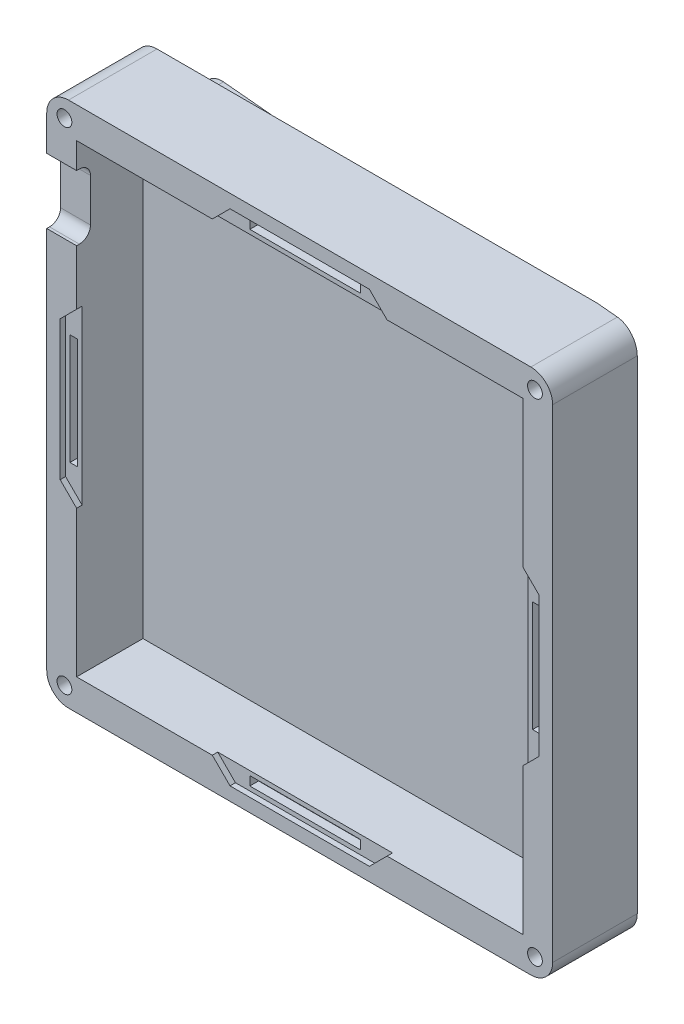
SolidWorks part; units mm, degrees
ref_plane "Front Plane" through (0, 0, 0) normal (1, 0, 0) x (0, 1, 0)
ref_plane "Top Plane" through (0, 0, 0) normal (0, 0, 1) x (0, 1, 0)
ref_plane "Right Plane" through (0, 0, 0) normal (0, 1, 0) x (-1, 0, 0)
sketch "Sketch1" plane through (0, 0, 0) normal (0, 0, 1) x (0, 1, 0)
  line L1 (-55.3847, -53.0098) -> (55.3847, -53.0098) construction
  line L2 (-55.3847, -53.0098) -> (-55.3847, 53.0098) construction
  line L3 (-55.3847, 53.0098) -> (55.3847, 53.0098) construction
  line L4 (55.3847, -53.0098) -> (55.3847, 53.0098) construction
  line L5 (-55.3847, -53.0098) -> (55.3847, 53.0098) construction
  line L6 (-55.3847, 53.0098) -> (55.3847, -53.0098) construction
  line L7 (-60.4647, -58.0898) -> (60.4647, -58.0898)
  line L8 (-60.4647, -58.0898) -> (-60.4647, 58.0898)
  line L9 (-60.4647, 58.0898) -> (60.4647, 58.0898)
  line L10 (60.4647, -58.0898) -> (60.4647, 58.0898)
  line L11 (-60.4647, -58.0898) -> (60.4647, 58.0898) construction
  line L12 (-60.4647, 58.0898) -> (60.4647, -58.0898) construction
  line L13 (-52.3875, -50.0126) -> (52.3875, -50.0126) construction
  line L14 (-52.3875, -50.0126) -> (-52.3875, 50.0126) construction
  line L15 (-52.3875, 50.0126) -> (52.3875, 50.0126) construction
  line L16 (52.3875, -50.0126) -> (52.3875, 50.0126) construction
  line L17 (-52.3875, -50.0126) -> (52.3875, 50.0126) construction
  line L18 (-52.3875, 50.0126) -> (52.3875, -50.0126) construction
  point P0 (0, 0)
  point P6 (0, 0)
  point P11 (0, 0)
  dimension "D1" = 106.0196
  dimension "D2" = 110.7694
  dimension "D3" = 5.08
  dimension "D4" = 5.08
  dimension "D5" = 104.775
  dimension "D6" = 100.0252
extrude "Boss-Extrude1" add sketch "Sketch1" along normal blind 5.08
sketch "Sketch2" plane through (0, 0, 5.08) normal (0, 0, 1) x (1, 0, 0)
  line L1 (58.0898, -60.4647) -> (-58.0898, -60.4647)
  line L2 (58.0898, -60.4647) -> (58.0898, 60.4647)
  line L3 (58.0898, 60.4647) -> (-58.0898, 60.4647)
  line L4 (-58.0898, -60.4647) -> (-58.0898, 60.4647)
  line L5 (58.0898, -60.4647) -> (-58.0898, 60.4647) construction
  line L6 (58.0898, 60.4647) -> (-58.0898, -60.4647) construction
  line L7 (50.2688, -52.324) -> (-50.2688, -52.324) construction
  line L8 (50.2688, -52.324) -> (50.2688, 52.324) construction
  line L9 (50.2688, 52.324) -> (-50.2688, 52.324) construction
  line L10 (-50.2688, -52.324) -> (-50.2688, 52.324) construction
  line L11 (50.2688, -52.324) -> (-50.2688, 52.324) construction
  line L12 (50.2688, 52.324) -> (-50.2688, -52.324) construction
  line L13 (-51.2296, -53.324) -> (51.2296, -53.324)
  line L14 (-51.2296, -53.324) -> (-51.2296, 53.324)
  line L15 (-51.2296, 53.324) -> (51.2296, 53.324)
  line L16 (51.2296, -53.324) -> (51.2296, 53.324)
  line L17 (-51.2296, -53.324) -> (51.2296, 53.324) construction
  line L18 (-51.2296, 53.324) -> (51.2296, -53.324) construction
  point P0 (0, 0)
  point P7 (0, 0)
  point P12 (0, 0)
  dimension "D1" = 104.648
  dimension "D2" = 1
extrude "Boss-Extrude2" add sketch "Sketch2" along normal blind 15.24
sketch "Sketch3" plane through (0, 0, 20.32) normal (0, 0, 1) x (1, 0, 0)
  line L0 (-50.0126, 0) -> (50.0126, 0) construction
  line L1 (-50.0126, -52.3875) -> (-21, -52.3875)
  line L2 (-50.0126, -52.3875) -> (-50.0126, -21)
  line L3 (-50.0126, 52.3875) -> (-21, 52.3875)
  line L4 (50.0126, -52.3875) -> (50.0126, -21)
  line L5 (-50.0126, -52.3875) -> (50.0126, 52.3875) construction
  line L6 (-50.0126, 52.3875) -> (50.0126, -52.3875) construction
  line L7 (0, 52.3875) -> (0, -52.3875) construction
  line L8 (50.0126, 0) -> (55.0126, 0) construction
  line L9 (55.0126, -16) -> (55.0126, 16)
  line L10 (50.0126, 21) -> (50.0126, 52.3875)
  line L11 (50.0126, -21) -> (50.0126, 21) construction
  line L12 (55.0126, 16) -> (50.0126, 21)
  line L13 (55.0126, -16) -> (50.0126, -21)
  line L14 (-21, -52.3875) -> (21, -52.3875) construction
  line L15 (21, -52.3875) -> (50.0126, -52.3875)
  line L16 (-50.0126, -21) -> (-50.0126, 21) construction
  line L17 (-50.0126, 21) -> (-50.0126, 52.3875)
  line L18 (-21, 52.3875) -> (21, 52.3875) construction
  line L19 (21, 52.3875) -> (50.0126, 52.3875)
  line L20 (0, 52.3875) -> (0, 57.3875) construction
  line L21 (-50.0126, 0) -> (-55.0126, 0) construction
  line L22 (0, -52.3875) -> (0, -57.3875) construction
  line L23 (-16, -57.3875) -> (16, -57.3875)
  line L24 (-55.0126, 16) -> (-55.0126, -16)
  line L25 (-16, 57.3875) -> (16, 57.3875)
  line L26 (16, 57.3875) -> (21, 52.3875)
  line L27 (-21, 52.3875) -> (-16, 57.3875)
  line L28 (-55.0126, 16) -> (-50.0126, 21)
  line L29 (-50.0126, -21) -> (-55.0126, -16)
  line L30 (-16, -57.3875) -> (-21, -52.3875)
  line L31 (16, -57.3875) -> (21, -52.3875)
  point P0 (0, 0)
  point P13 (55.0126, 0)
  point P31 (0, -57.3875)
  point P32 (-55.0126, 0)
  point P33 (0, 57.3875)
  dimension "D1" = 104.775
  dimension "D2" = 100.0252
  dimension "D3" = 5
  dimension "D4" = 32
  dimension "D5" = 135
  dimension "D6" = 135
  dimension "D7" = 135
  dimension "D8" = 135
extrude "Cut-Extrude1" cut sketch "Sketch3" against normal blind 1.25
sketch "Sketch4" plane through (0, 0, 19.07) normal (0, 0, 1) x (1, 0, 0)
  line L0 (16, 57.3875) -> (-16, 57.3875) construction
  line L1 (-12.7, 56.3875) -> (12.7, 56.3875)
  line L2 (-12.7, 56.3875) -> (-12.7, 54.324)
  line L3 (-12.7, 54.324) -> (12.7, 54.324)
  line L4 (12.7, 56.3875) -> (12.7, 54.324)
  line L5 (51.2296, 53.324) -> (-51.2296, 53.324) construction
  line L6 (11.176, 0) -> (-11.176, 0) construction
  line L7 (0, 57.3875) -> (0, 56.3875) construction
  line L8 (-12.7, -54.324) -> (12.7, -54.324)
  line L9 (12.7, -56.3875) -> (12.7, -54.324)
  line L10 (-12.7, -56.3875) -> (12.7, -56.3875)
  line L11 (-12.7, -56.3875) -> (-12.7, -54.324)
  line L12 (-55.0126, 16) -> (-55.0126, -16) construction
  line L13 (-54.0126, 12.7) -> (-52.2296, 12.7)
  line L14 (-54.0126, 12.7) -> (-54.0126, -12.7)
  line L15 (-54.0126, -12.7) -> (-52.2296, -12.7)
  line L16 (-52.2296, 12.7) -> (-52.2296, -12.7)
  line L17 (-51.2296, 53.324) -> (-51.2296, -53.324) construction
  line L18 (-55.0126, 16) -> (-55.0126, -16) construction
  line L19 (-55.0126, 0) -> (-54.0126, 0) construction
  line L20 (0, -11.176) -> (0, 11.176) construction
  line L21 (54.0126, -12.7) -> (52.2296, -12.7)
  line L22 (52.2296, 12.7) -> (52.2296, -12.7)
  line L23 (54.0126, 12.7) -> (52.2296, 12.7)
  line L24 (54.0126, 12.7) -> (54.0126, -12.7)
  point P8 (0, 57.3875)
  point P10 (0, 56.3875)
  point P26 (-54.0126, 0)
  point P27 (-55.0126, 0)
  dimension "D1" = 25.4
  dimension "D2" = 1
  dimension "D3" = 1
  dimension "D4" = 1
  dimension "D5" = 1
  dimension "D6" = 25.4
extrude "Cut-Extrude2" cut sketch "Sketch4" against normal blind 2
sketch "Sketch5" plane through (-58.0898, 0, 0) normal (-1, 0, 0) x (0, -1, 0)
  line L0 (-60.4647, 20.32) -> (-60.4647, 0) construction
  line L1 (-43.0911, 23.3172) -> (-36.6903, 23.3172) construction
  line L2 (-44.3611, 22.0472) -> (-44.3611, 21.4122) construction
  line L3 (-43.0911, 20.1422) -> (-36.6903, 20.1422) construction
  line L4 (-35.4203, 22.0472) -> (-35.4203, 21.4122) construction
  line L5 (60.4647, 20.32) -> (60.4647, 0) construction
  line L6 (-60.4647, 0) -> (60.4647, 0) construction
  line L7 (-39.8907, 23.3172) -> (-39.8907, 26.3172) construction
  line L8 (-44.8211, 26.3172) -> (-34.9603, 26.3172)
  line L9 (-47.3611, 23.7772) -> (-47.3611, 19.6822)
  line L10 (-44.8211, 17.1422) -> (-34.9603, 17.1422)
  line L11 (-32.4203, 23.7772) -> (-32.4203, 19.6822)
  line L12 (-39.8907, 20.1422) -> (-39.8907, 17.1422) construction
  line L13 (-47.3611, 21.7297) -> (-44.3611, 21.7297) construction
  line L14 (-35.4203, 21.7297) -> (-32.4203, 21.7297) construction
  arc A0 (-36.6903, 20.1422) -> (-35.4203, 21.4122) centre (-36.6903, 21.4122) ccw construction
  arc A1 (-44.3611, 21.4122) -> (-43.0911, 20.1422) centre (-43.0911, 21.4122) ccw construction
  arc A2 (-43.0911, 23.3172) -> (-44.3611, 22.0472) centre (-43.0911, 22.0472) ccw construction
  arc A3 (-36.6903, 23.3172) -> (-35.4203, 22.0472) centre (-36.6903, 22.0472) cw construction
  arc A4 (-34.9603, 17.1422) -> (-32.4203, 19.6822) centre (-34.9603, 19.6822) ccw
  arc A5 (-34.9603, 26.3172) -> (-32.4203, 23.7772) centre (-34.9603, 23.7772) cw
  arc A6 (-44.8211, 26.3172) -> (-47.3611, 23.7772) centre (-44.8211, 23.7772) ccw
  arc A7 (-47.3611, 19.6822) -> (-44.8211, 17.1422) centre (-44.8211, 19.6822) ccw
  point P22 (-39.8907, 26.3172)
  point P23 (-39.8907, 23.3172)
  point P28 (-32.4203, 21.7297)
  point P29 (-35.4203, 21.7297)
  point P30 (-44.3611, 21.7297)
  point P31 (-47.3611, 21.7297)
  dimension "D5" = 1.27
  dimension "D8" = 2.54
  dimension "D1" = 16.1036
  dimension "D2" = 95.885
  dimension "D3" = 23.3172
  dimension "D4" = 20.1422
  dimension "D6" = 3
  dimension "D7" = 3
extrude "Cut-Extrude3" cut sketch "Sketch5" against normal blind 9.906
sketch "Sketch6" plane through (0, 0, 0) normal (0, 0, -1) x (1, 0, 0)
  line L0 (58.0898, 60.4647) -> (58.0898, -60.4647) construction
  line L1 (-51.1302, 53.3273) -> (58.0898, 53.3273)
  line L2 (-51.1302, 53.3273) -> (-51.1302, -53.3273)
  line L3 (-51.1302, -53.3273) -> (58.0898, -53.3273)
  line L4 (58.0898, 53.3273) -> (58.0898, -53.3273)
  line L5 (-58.0898, 60.4647) -> (58.0898, 60.4647) construction
  point P6 (58.0898, 0)
  point P7 (58.0898, 0)
  dimension "D1" = 7.1374
  dimension "D2" = 109.22
sketch "Sketch7" plane through (0, 0, 0) normal (0, 0, -1) x (1, 0, 0)
  line L0 (-58.0898, 60.4647) -> (-54.0258, 56.4007) construction
  line L1 (-58.0898, 60.4647) -> (58.0898, 60.4647) construction
  circle A0 centre (-54.0258, 56.4007) radius 3
  dimension "D2" = 6
  dimension "D1" = 45
  dimension "D3" = 4.064
extrude "Cut-Extrude4" cut sketch "Sketch7" against normal blind 12.32
sketch "Sketch8" plane through (0, 0, 12.32) normal (0, 0, -1) x (1, 0, 0)
  line L0 (-57.0258, 56.4007) -> (-51.0258, 56.4007) construction
  circle A0 centre (-54.0258, 56.4007) radius 3 construction
  circle A1 centre (-54.0258, 56.4007) radius 3 construction
  circle A2 centre (-54.0258, 56.4007) radius 1.7
  dimension "D1" = 3.4
extrude "Cut-Extrude5" cut sketch "Sketch8" against normal blind 12.32
mirror "Mirror1" about plane through (0, 0, 0) normal (0, 1, 0) of "Cut-Extrude5", "Cut-Extrude4" second plane through (0, 0, 0) second plane normal (1, 0, 0)
extrude "Boss-Extrude3" add sketch "Sketch6" along normal blind 9.5504
fillet "Fillet1" radius 5.08 2 edges at (-51.1302, 53.3273, -4.7752) (-51.1302, -53.3273, -4.7752)
fillet "Fillet2" radius 5 4 edges at (-58.0898, 60.4647, 10.16) (-58.0898, -60.4647, 10.16) (58.0898, -60.4647, 10.16) (58.0898, 60.4647, 10.16)
sketch "Sketch10" plane through (0, 53.3273, 0) normal (0, 1, 0) x (-1, 0, 0)
  line L0 (-53.0898, 0) -> (53.0898, 0) construction
  line L1 (-58.0898, 0.8889) -> (51.1302, -8.6666)
  line L2 (-58.0898, 0) -> (-58.0898, 20.32) construction
  line L3 (51.1302, 0) -> (51.1302, -9.5504) construction
  line L4 (-58.0898, 0.8889) -> (-58.0898, -9.5504)
  line L5 (-58.0898, -9.5504) -> (51.1302, -9.5504)
  line L6 (51.1302, -9.5504) -> (51.1302, -8.6666)
  point P0 (-47.9298, 0)
  dimension "D1" = 10.16
  dimension "D2" = 5
extrude "Cut-Extrude6" cut sketch "Sketch10" against normal blind 130.048 and the other way blind 18.034
